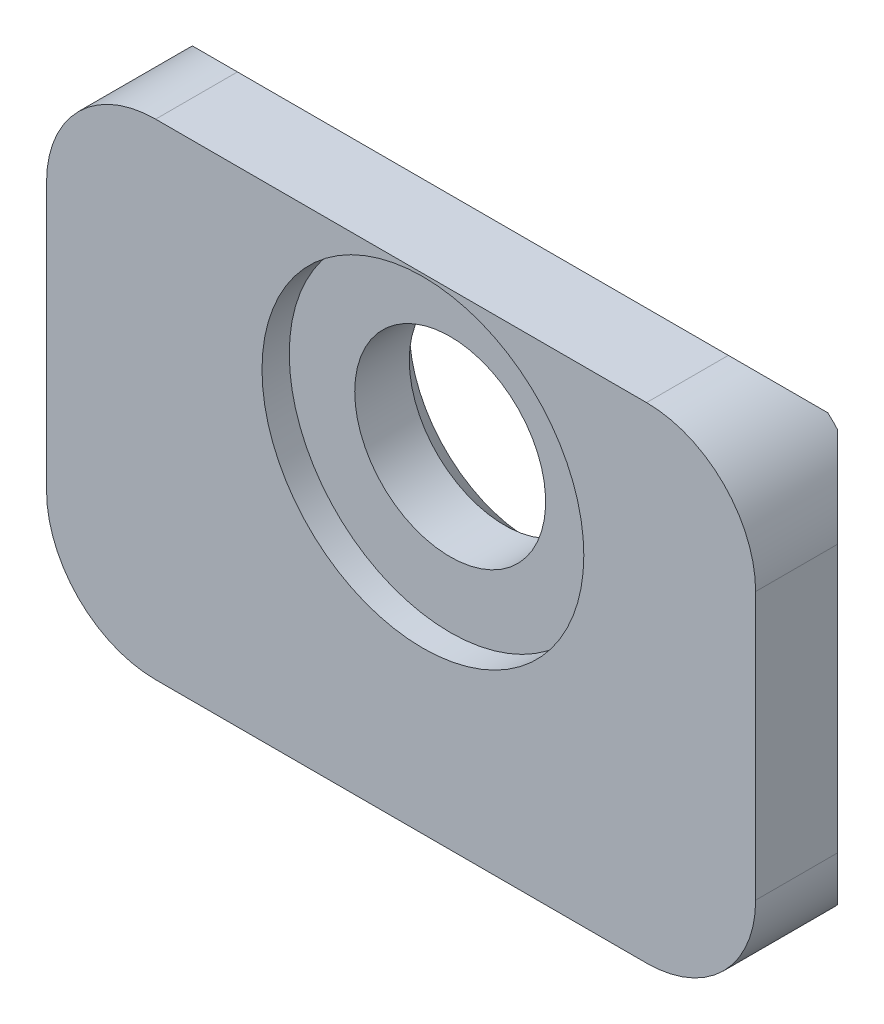
SolidWorks part; units mm, degrees
material "ABS"
ref_plane "Top Plane" through (0, 0, 0) normal (0, 0, 1) x (1, 0, 0)
ref_plane "Front Plane" through (0, 0, 0) normal (0, 1, 0) x (1, 0, 0)
ref_plane "Right Plane" through (0, 0, 0) normal (1, 0, 0) x (0, 0, -1)
sketch "Sketch1" plane through (0, 0, 0) normal (0, 0, 1) x (1, 0, 0)
  line L1 (-6.5, -4.45) -> (6.5, -4.45)
  line L2 (-6.5, -4.45) -> (-6.5, 4.45)
  line L3 (-6.5, 4.45) -> (6.5, 4.45)
  line L4 (6.5, -4.45) -> (6.5, 4.45)
  line L5 (-6.5, -4.45) -> (6.5, 4.45) construction
  line L6 (-6.5, 4.45) -> (6.5, -4.45) construction
  point P0 (0, 0)
  dimension "D1" = 13
  dimension "D2" = 8.9
extrude "Boss-Extrude1" add sketch "Sketch1" along normal blind 2
sketch "Sketch2" plane through (0, 0, 2) normal (0, 0, 1) x (1, 0, 0)
  line L0 (6.5, 4.45) -> (-6.5, 4.45) construction
  line L1 (-6.5, 4.45) -> (-6.5, -4.45) construction
  circle A0 centre (-0.4, 1.45) radius 1.75
  dimension "D3" = 3.5
  dimension "D1" = 3
  dimension "D2" = 6.1
extrude "Cut-Extrude4" cut sketch "Sketch2" against normal through all
sketch "Sketch3" plane through (0, 0, 2) normal (0, 0, 1) x (1, 0, 0)
  circle A0 centre (-0.4, 1.45) radius 2.95
  dimension "D1" = 5.9
extrude "Cut-Extrude9" cut sketch "Sketch3" against normal blind 0.5
chamfer "Chamfer1" distance 0.5 angle 45 5 edges at (0, 4.45, 0) (-6.5, 0, 0) (0, -4.45, 0) (6.5, 0, 0) (1.35, 1.45, 0)
fillet "Fillet2" radius 2 4 edges at (-6.5, 4.45, 1.25) (6.5, 4.45, 1.25) (6.5, -4.45, 1.25) (-6.5, -4.45, 1.25)
mirror "Mirror1" about plane through (6.5, -4.45, 2) normal (-1, 0, 0) of bodies 103
delete or keep bodies "Body-Delete/Keep 1" type delete bodies bodies 103
